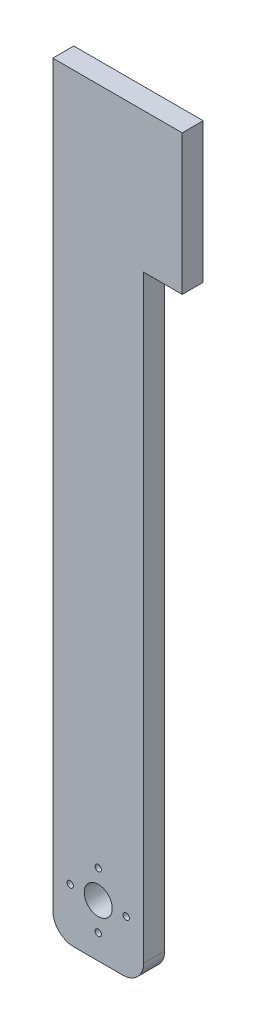
SolidWorks part; units mm, degrees
ref_plane "Plan de face" through (0, 0, 0) normal (0, 0, 1) x (1, 0, 0)
ref_plane "Plan de dessus" through (0, 0, 0) normal (0, 1, 0) x (1, 0, 0)
ref_plane "Plan de droite" through (0, 0, 0) normal (1, 0, 0) x (0, 0, -1)
sketch "Esquisse1" plane through (0, 0, 0) normal (0, 0, 1) x (1, 0, 0)
  line L0 (24.9164, -77.5735) -> (24.9164, 93.4265)
  line L1 (24.9164, 133.4265) -> (50.9164, 133.4265)
  line L2 (37.9164, 189.4329) -> (37.9164, -108.4772) construction
  line L3 (30.9164, -83.5735) -> (44.9164, -83.5735)
  line L4 (24.9164, 93.4265) -> (24.9164, 133.4265)
  line L6 (61.9164, 133.4265) -> (61.9164, 93.4265)
  line L9 (50.9164, 93.4265) -> (61.9164, 93.4265)
  line L10 (50.9164, 133.4265) -> (61.9164, 133.4265)
  line L11 (50.9164, -77.5735) -> (50.9164, 93.4265)
  arc A0 (44.9164, -83.5735) -> (50.9164, -77.5735) centre (44.9164, -77.5735) ccw
  arc A1 (24.9164, -77.5735) -> (30.9164, -83.5735) centre (30.9164, -77.5735) ccw
  circle A2 centre (29.9164, -68.5735) radius 0.9
  circle A3 centre (37.9164, -60.5735) radius 0.9
  circle A4 centre (45.9164, -68.5735) radius 0.9
  circle A5 centre (37.9164, -76.5735) radius 0.9
  circle A7 centre (37.9164, -68.5735) radius 4
  point P6 (50.9164, -83.5735)
  dimension "D3" = 6
  dimension "D11" = 40
  dimension "D10" = 11
  dimension "D6" = 1.8
  dimension "D7" = 1.8
  dimension "D8" = 1.8
  dimension "D9" = 1.8
  dimension "D4" = 8
  dimension "D1" = 217
  dimension "D2" = 26
  dimension "D5" = 15
extrude "Boss.-Extru.1" add sketch "Esquisse1" along normal blind 6
